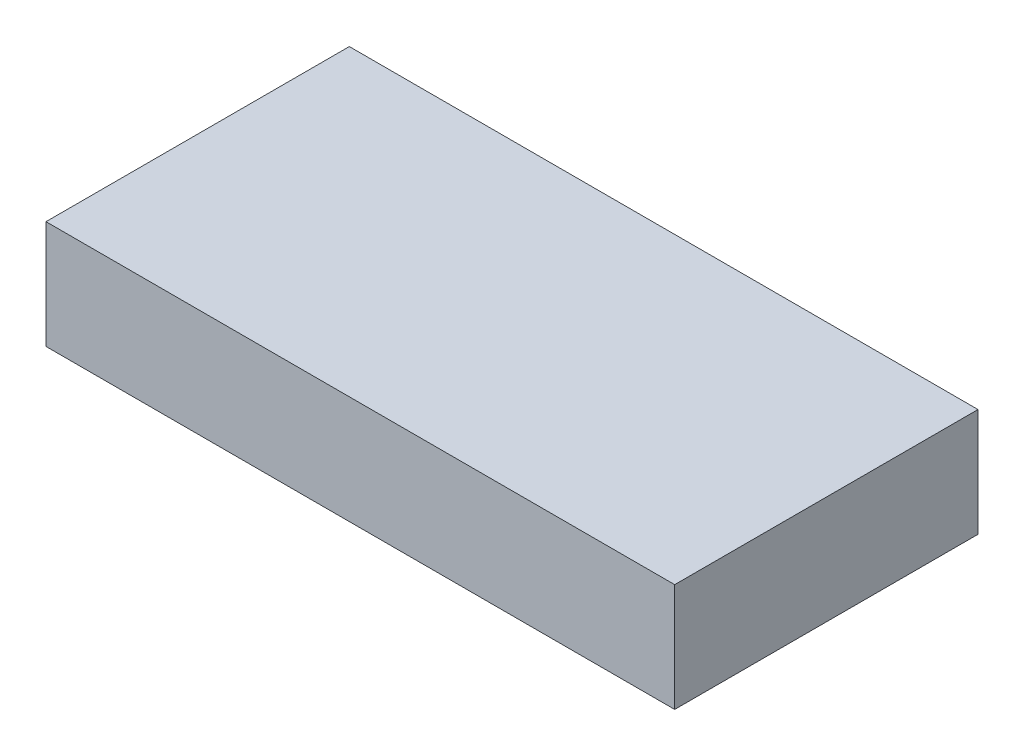
SolidWorks part; units mm, degrees
ref_plane "Front Plane" through (0, 0, 0) normal (0, 0, 1) x (1, 0, 0)
ref_plane "Top Plane" through (0, 0, 0) normal (0, 1, 0) x (1, 0, 0)
ref_plane "Right Plane" through (0, 0, 0) normal (1, 0, 0) x (0, 0, -1)
sketch "Sketch1" plane through (0, 0, 0) normal (0, 1, 0) x (1, 0, 0)
  line L1 (570, -275) -> (-570, -275)
  line L2 (570, -275) -> (570, 275)
  line L3 (570, 275) -> (-570, 275)
  line L4 (-570, -275) -> (-570, 275)
  line L5 (570, -275) -> (-570, 275) construction
  line L6 (570, 275) -> (-570, -275) construction
  point P0 (0, 0)
  dimension "D1" = 1140
  dimension "D2" = 550
extrude "Boss-Extrude1" add sketch "Sketch1" along normal blind 196
equation "\"assembly\" = 0"
equation "\"thickness 1\" = 3"
equation "\"thickness 2\" = 8"
equation "\"connecting flange\" = 35"
equation "\"main\" = 0"
equation "\"main length\" = 1200"
equation "\"main width\" = 1200"
equation "\"divider panel distance offset\" = 550"
equation "\"side panel\" = 0"
equation "\"access hatch length\" = 600"
equation "\"access hatch width\" = 450"
equation "\"access hatch offset X\" = 100"
equation "\"access hatch offset Y\" = 100"
equation "\"side panel length\" = 1200"
equation "\"side panel width\" = 1000"
equation "\"back panel\" = 0"
equation "\"back panel access hatch length\" = 1150"
equation "\"back panel access hatch width\" = 206"
equation "\"back panel access hatch flange\" = 40"
equation "\"drift eliminator\" = 0"
equation "\"drift eliminator size offset\" = 10"
equation "\"drift eliminator length\" = \"back panel access hatch length\" - \"drift eliminator size offset\""
equation "\"drift eliminator width\" = \"back panel access hatch width\" - \"drift eliminator size offset\""
equation "\"drift eliminator depth\" = \"divider panel distance offset\""
equation "\"sump\" = 0"
equation "\"D1@Boss-Extrude1\"=\"drift eliminator width\""
equation "\"D1@Sketch1\"=\"drift eliminator length\""
equation "\"D2@Sketch1\"=\"drift eliminator depth\""
